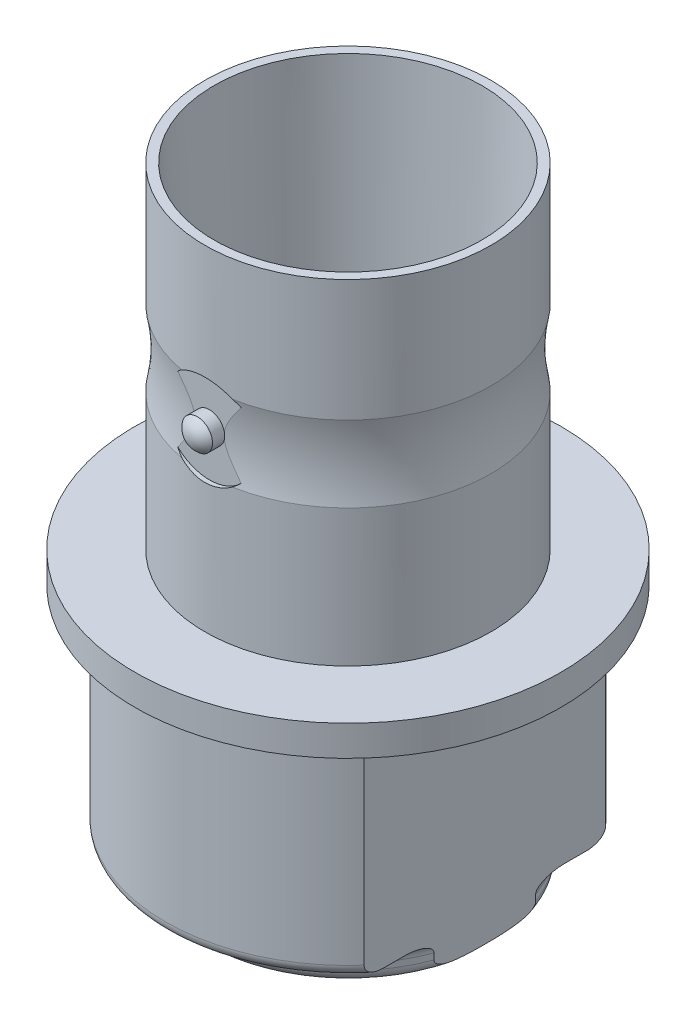
SolidWorks part; units mm, degrees
material "Хромированная нержавеющая сталь"
ref_plane "Спереди" through (0, 0, 0) normal (0, 0, 1) x (1, 0, 0)
ref_plane "Сверху" through (0, 0, 0) normal (0, 1, 0) x (1, 0, 0)
ref_plane "Справа" through (0, 0, 0) normal (1, 0, 0) x (0, 0, -1)
sketch "Эскиз1" plane through (0, 0, 0) normal (1, 0, 0) x (0, 0, -1)
  line L0 (0, 0) -> (0, 20) construction
  line L1 (4.7, 20) -> (4.7, 16)
  line L2 (4, 8) -> (3, 8)
  line L3 (-3, 8) -> (3, 8) construction
  line L4 (5.6, 1) -> (5.2, 1)
  line L5 (4.7, 13.5) -> (4.7, 9)
  line L6 (4.7, 9) -> (7, 9)
  line L7 (7, 9) -> (7, 8)
  line L8 (7, 8) -> (6, 8)
  line L9 (6, 8) -> (6, 1.4)
  line L10 (4.8, 0.6) -> (4.8, 0.4)
  line L11 (-4, 8) -> (4, 8) construction
  line L12 (4.4, 20) -> (4.7, 20)
  line L13 (4.4, 0) -> (3, 0)
  line L14 (4, 8) -> (4.4, 20)
  line L15 (3, 8) -> (3, 0)
  arc A0 (4.7, 16) -> (4.7, 13.5) centre (10.9, 14.75) ccw
  arc A1 (4.4, 0) -> (4.8, 0.4) centre (4.4, 0.4) ccw
  arc A2 (5.2, 1) -> (4.8, 0.6) centre (5.2, 0.6) ccw
  arc A3 (6, 1.4) -> (5.6, 1) centre (5.6, 1.4) cw
  point P22 (4.8, 1)
  point P25 (6, 1)
  dimension "D6" = 8
  dimension "D14" = 1.2
  dimension "D13" = 1
  dimension "D15" = 0.4
  dimension "D1" = 20
  dimension "D2" = 9.4
  dimension "D3" = 0.3
  dimension "D4" = 4
  dimension "D5" = 2.5
  dimension "D7" = 11
  dimension "D8" = 1
  dimension "D9" = 12
  dimension "D10" = 14
  dimension "D11" = 1
  dimension "D12" = 12
  dimension "D16" = 4.5
revolve "Повернуть1" add sketch "Эскиз1" angle 360 about L0
cosmetic thread "Условное изображение резьбы1" parameters "D2"=10.619
ref_plane "Плоскость1" through (0, 0, 4.7) normal (0, 0, 1) x (1, 0, 0)
sketch "Эскиз2" plane through (0, 0, 0) normal (0, 0, 1) x (1, 0, 0)
  line L0 (0, 0) -> (0, 8) construction
  line L1 (-6, 8) -> (6, 8) construction
  line L3 (-4.5, 0) -> (4.5, 0)
  line L4 (-4.5, 0) -> (-4.5, 8)
  line L5 (-4.5, 8) -> (4.5, 8)
  line L6 (4.5, 0) -> (4.5, 8)
  line L7 (-4.5, 0) -> (4.5, 8) construction
  line L8 (-4.5, 8) -> (4.5, 0) construction
  line L9 (-7, 0) -> (7, 0)
  line L10 (-7, 0) -> (-7, 8)
  line L11 (-7, 8) -> (7, 8)
  line L12 (7, 0) -> (7, 8)
  line L13 (-7, 0) -> (7, 8) construction
  line L14 (-7, 8) -> (7, 0) construction
  point P5 (0, 4)
  point P10 (0, 4)
  dimension "D1" = 9
extrude "Вырез-Вытянуть1" cut sketch "Эскиз2" against normal mid plane 20 contours L11 L10 L9 L4 | L9 L12 L11 L6 region at (-5.75, 4, 0) region at (5.75, 4, 0)
sketch "Эскиз5" plane through (0, 0, 4.7) normal (0, 0, 1) x (1, 0, 0)
  circle A0 centre (0, 14.75) radius 1.5
  dimension "D1" = 3
extrude "Вырез-Вытянуть4" cut sketch "Эскиз5" against normal blind 0.15
sketch "Эскиз7" plane through (0, 0, 4.55) normal (0, 0, 1) x (1, 0, 0)
  circle A0 centre (0, 14.75) radius 0.5
  dimension "D1" = 1
extrude "Бобышка-Вытянуть1" add sketch "Эскиз7" along normal blind 0.4
dome "Купол1" faces to dome 1 distance 0.25 reverse direction no elliptical dome no face at (0.5, 14.75, 4.95) parameters "D1"=0.25
pattern_circular "Круговой массив1" count 2 over 360 about axis through (0, 9, 0) along (0, -1, 0) of "Купол1", "Бобышка-Вытянуть1", "Вырез-Вытянуть4"
